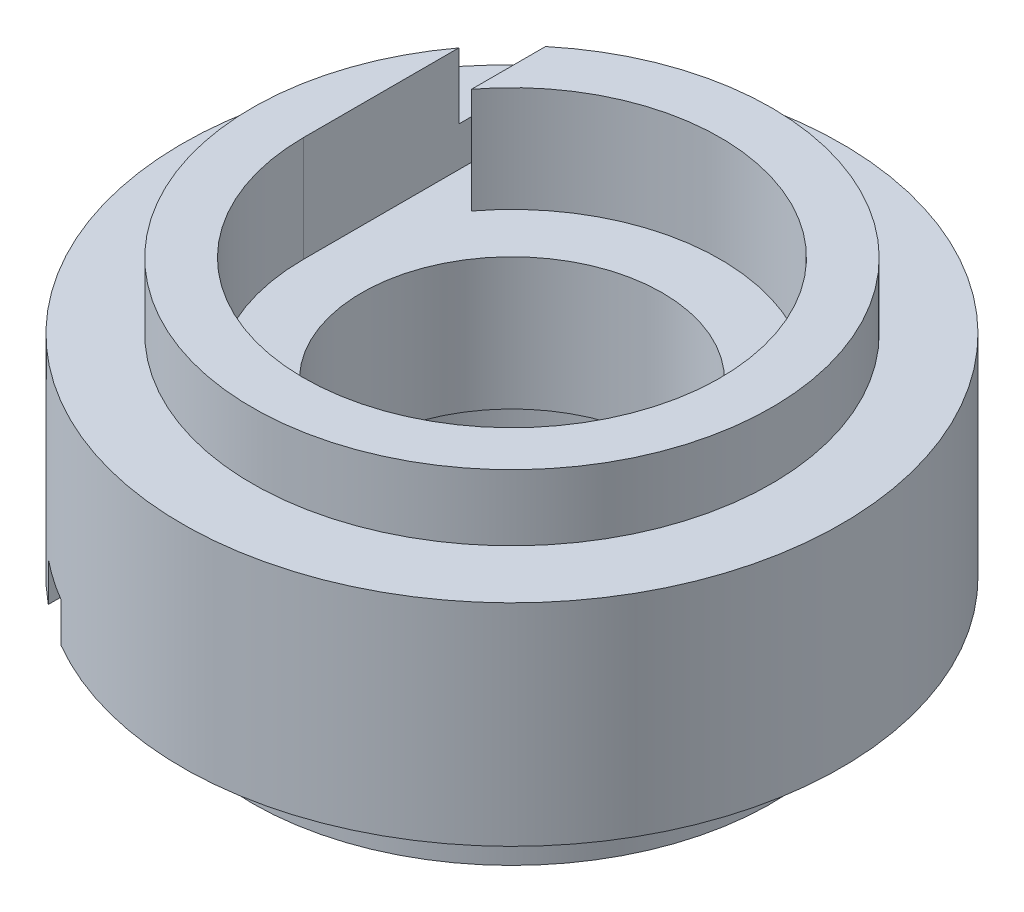
SolidWorks part; units mm, degrees
ref_plane "Front Plane" through (0, 0, 0) normal (0, 0, 1) x (1, 0, 0)
ref_plane "Top Plane" through (0, 0, 0) normal (0, 1, 0) x (1, 0, 0)
ref_plane "Right Plane" through (0, 0, 0) normal (1, 0, 0) x (0, 0, -1)
sketch "Sketch1" plane through (0, 0, 0) normal (0, 1, 0) x (1, 0, 0)
  circle A0 centre (0, 0) radius 31.75
  circle A1 centre (0, 0) radius 14.478
  dimension "D1" = 63.5
  dimension "D2" = 28.956
extrude "Boss-Extrude1" add sketch "Sketch1" along normal mid plane 33.02
sketch "Sketch2" plane through (0, 16.51, 0) normal (0, 1, 0) x (1, 0, 0)
  line L0 (-20.066, 0) -> (-20.066, 24.6052)
  line L1 (-16.002, 12.107) -> (-16.002, 27.4226)
  arc A0 (-20.066, 0) -> (-16.002, 12.107) centre (0, 0) ccw
  circle A1 centre (0, 0) radius 31.75 construction
  arc A2 (-16.002, 27.4226) -> (-20.066, 24.6052) centre (0, 0) ccw
  dimension "D1" = 4.064
extrude "Cut-Extrude1" cut sketch "Sketch2" against normal blind 10.16
sketch "Sketch13" plane through (0, 16.51, 0) normal (0, 1, 0) x (1, 0, 0)
  circle A1 centre (0, 0) radius 25.019
  circle A2 centre (0, 0) radius 31.75
  arc A3 (-20.066, 24.6052) -> (-16.002, 27.4226) centre (0, 0) ccw construction
  dimension "D1" = 50.038
extrude "Cut-Extrude2" cut sketch "Sketch13" against normal blind 6.35
sketch "Sketch5" plane through (0, 0, 0) normal (0, 1, 0) x (1, 0, 0)
  line L0 (0, -39.3443) -> (0, 40.2571) construction
  line L1 (0, -22.352) -> (0, 22.352) construction
ref_axis "Axis1" through (34.925, 0, 0) along (-1, 0, 0)
sketch "Sketch9" plane through (0, 0, 0) normal (0, 0, 1) x (1, 0, 0)
  line L0 (0, -22.352) -> (0, 22.352) construction
  line L1 (-20.066, 3.81) -> (-14.478, 3.81)
  line L2 (-20.066, 3.81) -> (-20.066, 0)
  line L3 (-20.066, 0) -> (-14.478, 0)
  line L4 (-14.478, 3.81) -> (-14.478, 0)
  point P5 (-14.478, 1.905)
  dimension "D1" = 3.81
  dimension "D2" = 14.478
sketch "Sketch12" plane through (0, 6.35, 0) normal (0, 1, 0) x (1, 0, 0)
  circle A0 centre (0, 0) radius 14.478
  circle A1 centre (0, 0) radius 14.478 construction
curve "Helix/Spiral2" pitch 3.302 height 2.9619 turns 0.897
pattern_circular "CirPattern1" count 2 every 180 about axis through (34.925, 0, 0) along (-1, 0, 0) of "Cut-Extrude2", "Cut-Extrude1"
